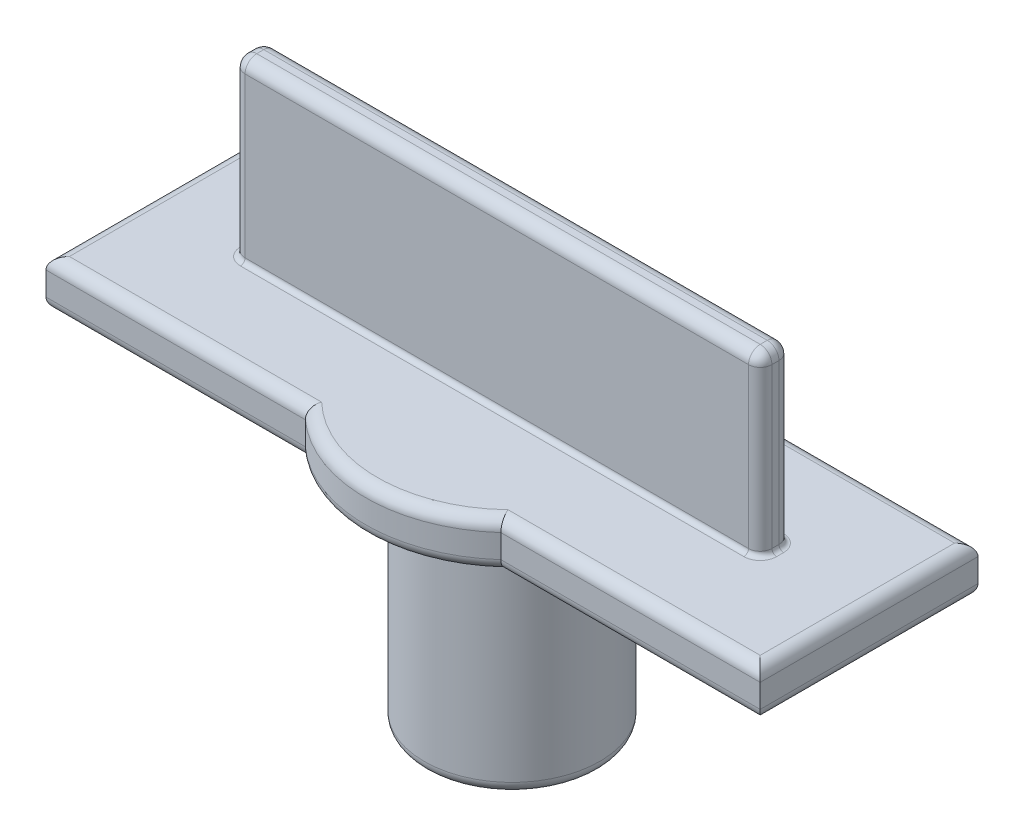
SolidWorks part; units mm, degrees
note: '?' marks a value the reader was unsure of.
ref_plane "Front Plane" through (0, 0, 0) normal (0, 0, 1) x (1, 0, 0)
ref_plane "Top Plane" through (0, 0, 0) normal (0, 1, 0) x (1, 0, 0)
ref_plane "Right Plane" through (0, 0, 0) normal (1, 0, 0) x (0, 0, -1)
sketch "Sketch1" plane through (0, 0, 0) normal (0, 1, 0) x (1, 0, 0)
  circle A0 centre (0, 0) radius 4.699
  circle A1 centre (0, 0) radius 9.525
  dimension "D1" = 9.398
  dimension "D2" = 19.05
extrude "Boss-Extrude1" add sketch "Sketch1" along normal blind 25.4
sketch "Sketch2" plane through (0, 25.4, 0) normal (0, 1, 0) x (1, 0, 0)
  circle A0 centre (0, 0) radius 1.5875
  circle A1 centre (0, 0) radius 15.875
  dimension "D1" = 3.175
  dimension "D2" = 31.75
extrude "Boss-Extrude2" add sketch "Sketch2" along normal blind 5.08
sketch "Sketch3" plane through (0, 30.48, 0) normal (0, 1, 0) x (1, 0, 0)
  line L1 (-28.575, -1.651) -> (28.575, -1.651)
  line L2 (-28.575, -1.651) -> (-28.575, 1.651)
  line L3 (-28.575, 1.651) -> (28.575, 1.651)
  line L4 (28.575, -1.651) -> (28.575, 1.651)
  line L5 (-28.575, -1.651) -> (28.575, 1.651) construction
  line L6 (-28.575, 1.651) -> (28.575, -1.651) construction
  point P0 (0, 0)
  dimension "D1" = 3.302
  dimension "D2" = 57.15
extrude "Boss-Extrude3" add sketch "Sketch3" along normal blind 19.05
sketch "Sketch4" plane through (0, 30.48, 0) normal (0, -1, 0) x (1, 0, 0)
  line L0 (-15.7889, -1.651) -> (-28.575, -1.651) construction
  line L1 (-38.735, 11.811) -> (38.735, 11.811)
  line L2 (-38.735, 11.811) -> (-38.735, -11.811)
  line L3 (-38.735, -11.811) -> (38.735, -11.811)
  line L4 (38.735, 11.811) -> (38.735, -11.811)
  line L5 (-38.735, 11.811) -> (38.735, -11.811) construction
  line L6 (-38.735, -11.811) -> (38.735, 11.811) construction
  line L7 (-28.575, -1.651) -> (-28.575, 1.651) construction
  point P0 (0, 0)
  dimension "D1" = 10.16
  dimension "D2" = 10.16
extrude "Boss-Extrude4" add sketch "Sketch4" along normal blind 5.08
sketch "Sketch5" plane through (0, 0, 0) normal (0, -1, 0) x (1, 0, 0)
  circle A0 centre (0, 0) radius 4.699
  circle A1 centre (0, 0) radius 4.699 construction
curve "Helix/Spiral1" pitch 1.5875 height 25.4 turns 16
ref_axis "Axis1" through (0, -2.4765, 0) along (0, 1, 0)?
ref_plane "Plane2" through (0, 0, 0) normal (0.7071, 0, 0.7071) x (0.7071, 0, -0.7071)
sketch "Sketch7" plane through (0, 0, 0) normal (0.7071, 0, 0.7071) x (0.7071, 0, -0.7071)
  line L0 (-4.699, 0) -> (-4.699, 0.6985)
  line L1 (-4.699, 0.6985) -> (-3.683, 0)
  line L2 (-9.525, 0) -> (9.525, 0) construction
  line L3 (-3.683, 0) -> (-4.699, -0.6985)
  line L4 (-4.699, -0.6985) -> (-4.699, 0)
  dimension "D1" = 1.016
  dimension "D2" = 1.397
sweep "Sweep1" add profiles "Sketch7" path "Helix/Spiral1"
sketch "Sketch11" plane through (0, 0, 0) normal (0, -1, 0) x (1, 0, 0)
  line L1 (-7.7205, 8.1459) -> (7.7205, 8.1459)
  line L2 (-7.7205, 8.1459) -> (-7.7205, -8.1459)
  line L3 (-7.7205, -8.1459) -> (7.7205, -8.1459)
  line L4 (7.7205, 8.1459) -> (7.7205, -8.1459)
  line L5 (-7.7205, 8.1459) -> (7.7205, -8.1459) construction
  line L6 (-7.7205, -8.1459) -> (7.7205, 8.1459) construction
  point P0 (0, 0)
extrude "Cut-Extrude1" cut sketch "Sketch11" along normal blind 5.08
sketch "Sketch12" plane through (0, 0, 0) normal (0, -1, 0) x (1, 0, 0)
  circle A0 centre (0, 0) radius 3.9688
  dimension "D1" = 7.9375
extrude "Cut-Extrude2" cut sketch "Sketch12" against normal blind 25.4
fillet "Fillet1" radius 1.27 8 edges at (28.575, 40.005, 1.651) (28.575, 40.005, -1.651) (-28.575, 40.005, 1.651) (-28.575, 40.005, -1.651) (0, 49.53, 1.651) (-28.575, 49.53, 0) (0, 49.53, -1.651) (28.575, 49.53, 0)
fillet "Fillet2" radius 1.27 8 edges at (0, 30.48, 15.875) (38.735, 30.48, 0) (24.6712, 30.48, 11.811) (-24.6712, 30.48, 11.811) (-38.735, 30.48, 0) (-24.6712, 30.48, -11.811) (0, 30.48, -15.875) (24.6712, 30.48, -11.811)
fillet "Fillet3" radius 1.27 9 edges at (24.6712, 25.4, -11.811) (38.735, 25.4, 0) (24.6712, 25.4, 11.811) (0, 25.4, 15.875) (-24.6712, 25.4, 11.811) (-38.735, 25.4, 0) (-24.6712, 25.4, -11.811) (0, 25.4, -15.875) (0, 0, 9.525)
fillet "Fillet4" radius 3.81 1 edges at (0, 25.4, 9.525)
fillet "Fillet5" radius 0.508 8 edges at (-28.203, 30.48, 1.279) (-28.575, 30.48, 0) (-28.203, 30.48, -1.279) (0, 30.48, -1.651) (28.203, 30.48, -1.279) (28.575, 30.48, 0) (28.203, 30.48, 1.279) (0, 30.48, 1.651)
